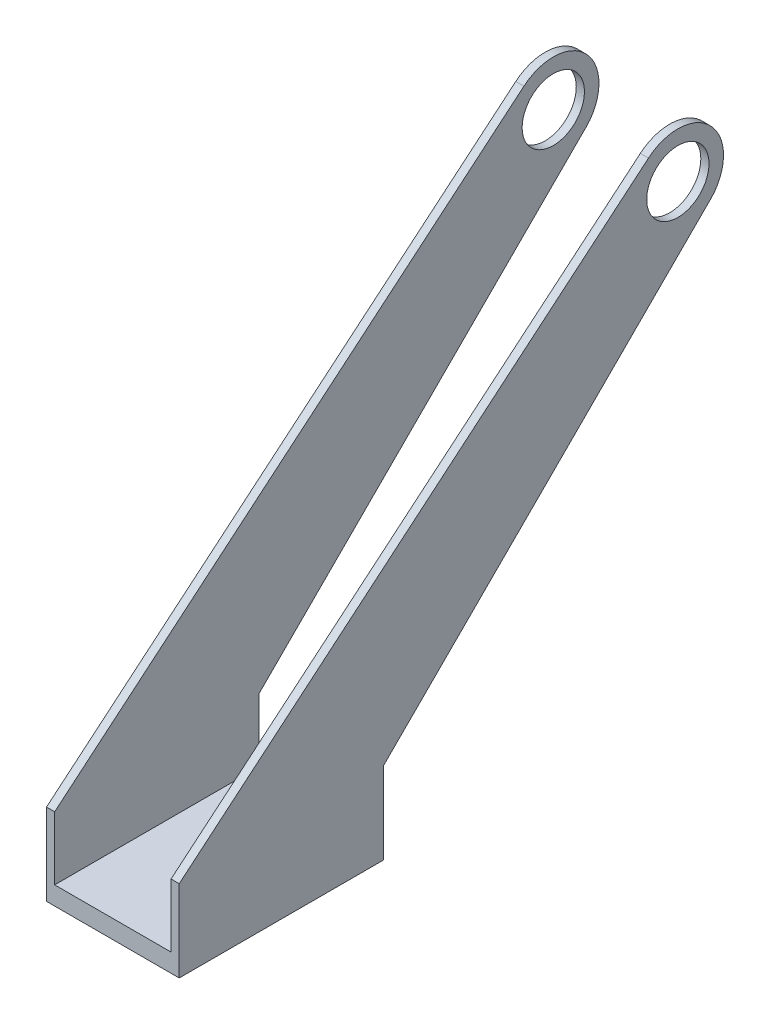
SolidWorks part; units mm, degrees
ref_plane "Alzado" through (0, 0, 0) normal (0, 0, 1) x (1, 0, 0)
ref_plane "Planta" through (0, 0, 0) normal (0, 1, 0) x (1, 0, 0)
ref_plane "Vista lateral" through (0, 0, 0) normal (1, 0, 0) x (0, 0, -1)
sketch "Croquis1" plane through (0, 0, 0) normal (1, 0, 0) x (0, 0, -1)
  line L0 (50, 20) -> (205.5635, 175.5634)
  line L2 (50, 20) -> (50, -20)
  line L3 (50, -20) -> (-50, -20)
  line L4 (-50, 20) -> (-50, -20)
  line L6 (205.5635, 175.5634) -> (208.568, 178.5679)
  line L7 (-50, 20) -> (179.8134, 212.8362)
  arc A0 (208.568, 178.5679) -> (179.8134, 212.8362) centre (194.1907, 195.702) ccw
  circle A1 centre (194.1907, 195.702) radius 15.25
  point P0 (0, 0)
  dimension "D1" = 40
  dimension "D2" = 100
  dimension "D3" = 300
  dimension "D6" = 220
extrude "Saliente-Extruir2" add sketch "Croquis1" along normal blind 70
sketch "Croquis3" plane through (0, 0, 50) normal (0, 0, 1) x (1, 0, 0)
  line L1 (70, -20) -> (0, -20) construction
  line L2 (6.5, -11) -> (6.5, 218.0691)
  line L3 (6.5, 218.0691) -> (63.5, 218.0691)
  line L4 (63.5, -11) -> (63.5, 218.0691)
  line L5 (70, 218.0691) -> (0, 218.0691) construction
  line L6 (0, 212.8362) -> (0, 20) construction
  line L7 (70, 212.8362) -> (70, 20) construction
  line L8 (6.5, -11) -> (63.5, -11)
  dimension "D1" = 6.5
  dimension "D2" = 6.5
  dimension "D3" = 9
extrude "Cortar-Extruir1" cut sketch "Croquis3" against normal through all
sketch "Croquis5" plane through (0, -20, 0) normal (0, -1, 0) x (1, 0, 0)
  circle A0 centre (35, 0) radius 10.7
  dimension "D1" = 21.4
extrude "Saliente-Extruir3" add sketch "Croquis5" along normal blind 15
extrude "Cortar-Extruir2" cut sketch "Croquis1<2>" along normal blind 2.5
sketch "Croquis1<2>" plane through (0, 0, 0) normal (1, 0, 0) x (0, 0, -1) same geometry as "Croquis1"
sketch "Croquis7" plane through (70, 0, 0) normal (1, 0, 0) x (0, 0, -1)
  line L0 (179.8134, 212.8362) -> (-50, 20)
  line L1 (-50, 20) -> (-50, -20)
  line L2 (-50, -20) -> (50, -20)
  line L3 (50, -20) -> (50, 20)
  line L4 (50, 20) -> (208.568, 178.5679)
  arc A0 (208.568, 178.5679) -> (179.8134, 212.8362) centre (194.1907, 195.702) ccw
  circle A1 centre (194.1907, 195.702) radius 15.25
extrude "Cortar-Extruir3" cut sketch "Croquis7" against normal blind 2.5
